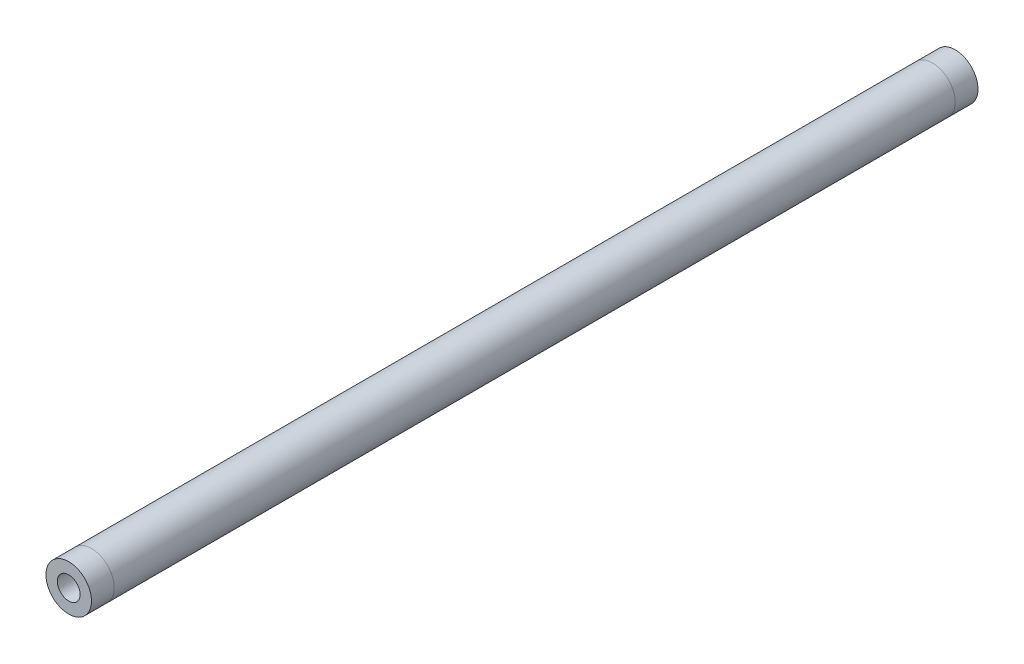
SolidWorks part; units mm, degrees
material "AISI 4130 Steel, normalized at 870C"
ref_plane "Front Plane" through (0, 0, 0) normal (0, 0, 1) x (1, 0, 0)
ref_plane "Top Plane" through (0, 0, 0) normal (0, 1, 0) x (1, 0, 0)
ref_plane "Right Plane" through (0, 0, 0) normal (1, 0, 0) x (0, 0, -1)
sketch "Axis" plane through (0, 0, 0) normal (1, 0, 0) x (0, 0, -1)
  line L0 (0, 0) -> (247.3338, 0) construction
  line L1 (247.3338, 0) -> (240.9838, 0)
  line L2 (247.3338, 0) -> (268.9238, 0) construction
  line L3 (0, 0) -> (-21.59, 0) construction
  line L4 (-21.59, 0) -> (-95.3875, 0)
  point P4 (0, 0)
  point P5 (247.3338, 0)
  point P6 (240.9838, 0)
  dimension "D1" = 6.35
  dimension "D2" = 21.59
  dimension "D3" = 21.59
sketch "Sketch1" plane through (0, 0, 0) normal (0, 0, 1) x (1, 0, 0)
  circle A0 centre (0, 0) radius 6.35
  circle A1 centre (0, 0) radius 4.8768
  circle A2 centre (0, 0) radius 3.175
  dimension "D1" = 12.7
  dimension "D2" = 1.4732
  dimension "D3" = 6.35
extrude "Threaded insert 1-1" add sketch "Sketch1" against normal blind 6.35 contours A0 A1 | A1 A2 region at (-6.1704, 0, 0) region at (-4.7389, 0, 0)
extrude "Threaded insert 1-2" add sketch "Sketch1<3>" against normal blind 6.35 from surface contours A1 A2 region at (-4.7389, 0, 0) starting at face at (6.35, 0, -6.35)
sketch "Sketch1<3>" plane through (0, 0, 0) normal (0, 0, 1) x (1, 0, 0) same geometry as "Sketch1"
extrude "Tube extrude" add sketch "Sketch1<4>" against normal up to vertex (240.9838 mm away) from surface separate body contours A0 A1 region at (-6.1704, 0, 0) up to point (0, 0, -240.9838) starting at face at (4.8768, 0, -6.35)
sketch "Sketch1<4>" plane through (0, 0, 0) normal (0, 0, 1) x (1, 0, 0) same geometry as "Sketch1"
extrude "Threaded insert 2-1" add sketch "Sketch1<6>" along normal blind 6.35 from surface separate body contours A1 A2 region at (-4.7389, 0, 0) starting at face at (4.8768, 0, -240.9838)
sketch "Sketch1<6>" plane through (0, 0, 0) normal (0, 0, 1) x (1, 0, 0) same geometry as "Sketch1"
extrude "Threaded insert 2-2" add sketch "Sketch1<9>" against normal blind 6.35 from surface separate body contours A1 A2 | A0 A1 region at (-6.1704, 0, 0) region at (-4.7389, 0, 0) starting at face at (4.8768, 0, -240.9838)
sketch "Sketch1<9>" plane through (0, 0, 0) normal (0, 0, 1) x (1, 0, 0) same geometry as "Sketch1"
combine bodies "Combine1" operation type add bodies to combine 106 104
equation "\"Threaded insert outer thickness\"= .25"
equation "\"D1@Threaded insert 1-1\"=\"Threaded insert outer thickness\""
equation "\"D1@Threaded insert 2-2\"=\"Threaded insert outer thickness\""
equation "\"D1@Axis\" = \"Threaded insert outer thickness\""
